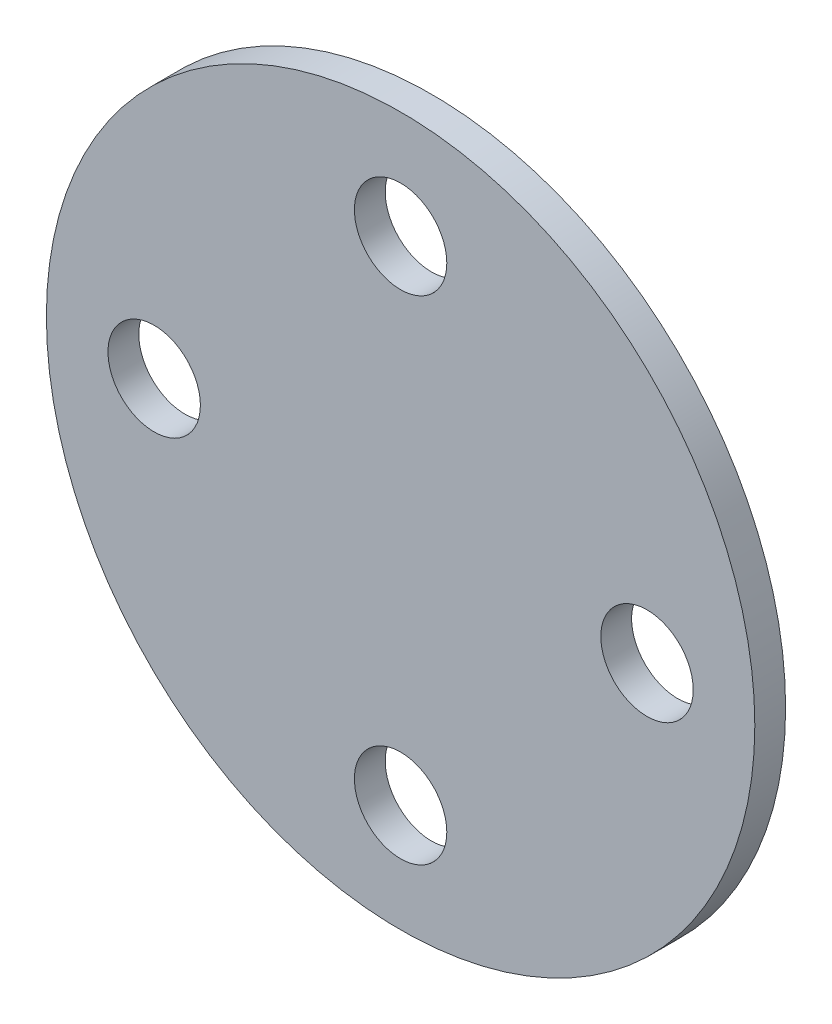
SolidWorks part; units mm, degrees
ref_plane "前视基准面" through (0, 0, 0) normal (0, 0, 1) x (1, 0, 0)
ref_plane "上视基准面" through (0, 0, 0) normal (0, 1, 0) x (1, 0, 0)
ref_plane "右视基准面" through (0, 0, 0) normal (1, 0, 0) x (0, 0, -1)
sketch "草图1" plane through (0, 0, 0) normal (0, 0, 1) x (1, 0, 0)
  circle A0 centre (0, 0) radius 23
  dimension "D1" = 46
extrude "凸台-拉伸1" add sketch "草图1" along normal blind 2
sketch "草图2" plane through (0, 0, 2) normal (0, 0, 1) x (1, 0, 0)
  line L0 (0, 16) -> (0, 0) construction
  line L1 (0, 0) -> (0, -16) construction
  line L2 (-16, 0) -> (0, 0) construction
  line L3 (0, 0) -> (16, 0) construction
  circle A0 centre (16, 0) radius 3
  circle A1 centre (0, 16) radius 3
  circle A2 centre (-16, 0) radius 3
  circle A3 centre (0, -16) radius 3
  dimension "D1" = 6
  dimension "D2" = 6
  dimension "D7" = 6
  dimension "D8" = 6
  dimension "D3" = 16
  dimension "D4" = 16
  dimension "D5" = 16
  dimension "D6" = 16
extrude "切除-拉伸1" cut sketch "草图2" against normal through all
